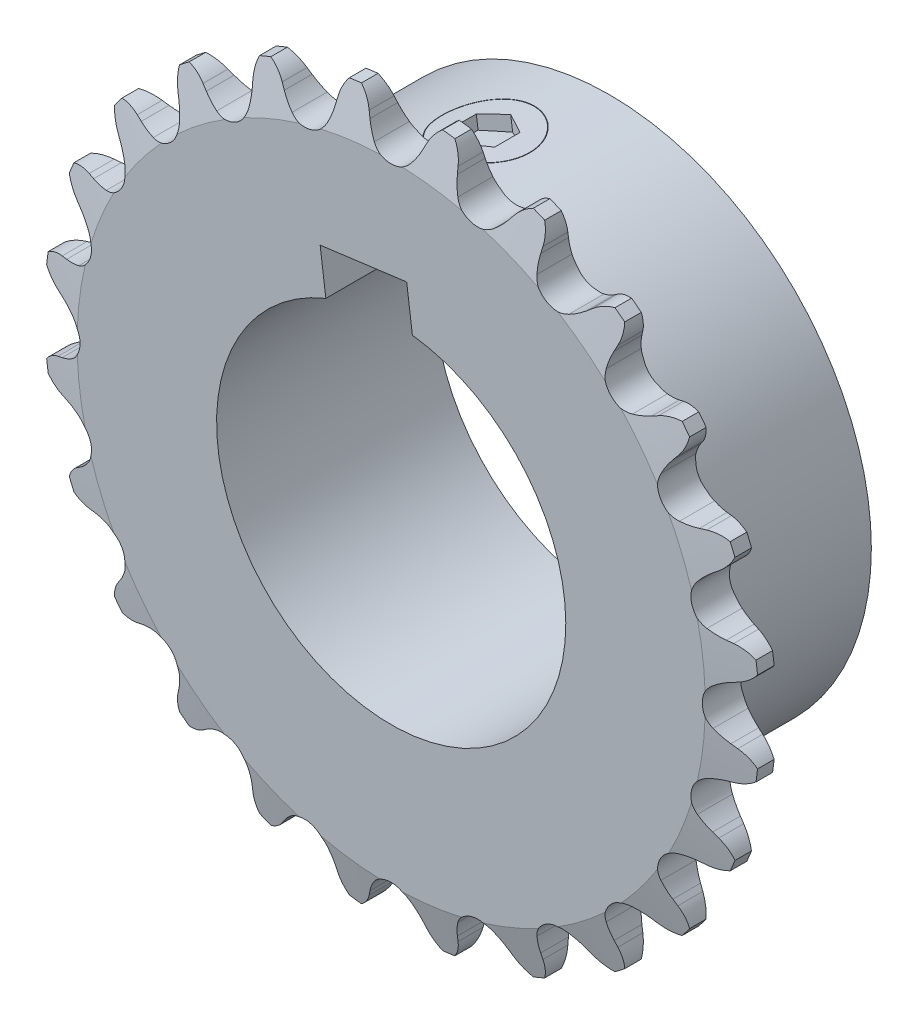
SolidWorks part; units mm, degrees
ref_plane "Front Plane" through (0, 0, 0) normal (0, 0, 1) x (1, 0, 0)
ref_plane "Top Plane" through (0, 0, 0) normal (0, 1, 0) x (1, 0, 0)
ref_plane "Right Plane" through (0, 0, 0) normal (1, 0, 0) x (0, 0, -1)
ref_axis "Axis1" through (0, 0, -88.99) along (0, 0, 1)
sketch "Sprocket-BaseSketch" plane through (0, 0, 0) normal (1, 0, 0) x (0, 0, -1)
  line L0 (1.397, 0) -> (1.397, 22.8465)
  line L1 (1.397, 22.8465) -> (0.6032, 26.0215)
  line L2 (0.6032, 26.0215) -> (-0.6032, 26.0215)
  line L3 (-0.6032, 26.0215) -> (-1.397, 22.8465)
  line L4 (-1.397, 22.8465) -> (-1.397, 0)
  line L5 (-1.397, 0) -> (1.397, 0)
  line L6 (5.588, 0) -> (-1.7463, 0) construction
  dimension "Hub Surface" = 1.397
  dimension "RightSide (1)" = 0.7938
  dimension "RightSide (2)" = 3.175
  dimension "OD" = 26.0215
  dimension "LeftSide (1)" = 0.7938
  dimension "LeftSide (2)" = 3.175
  dimension "Tooth Width" = 2.794
revolve "25 (04C) ANSI (ISO) Chain Number, 1.915in P.D." add sketch "Sprocket-BaseSketch" angle 360 about L6
sketch "Tooth-Sketch" plane through (0, 0, 0) normal (0, 0, 1) x (1, 0, 0)
  line L0 (0, 0) -> (0, 32.4328) construction
  line L1 (1.932, 24.319) -> (2.0923, 24.7192)
  line L2 (-1.932, 24.319) -> (-2.0923, 24.7192)
  line L3 (0, 24.3246) -> (6.2957, 23.4958) construction
  line L4 (0, 24.3246) -> (-6.2957, 23.4958) construction
  arc A0 (-1.3466, 23.2913) -> (1.3466, 23.2913) centre (0, 24.3246) ccw
  arc A1 (1.3466, 23.2913) -> (1.932, 24.319) centre (-2.0957, 25.9327) ccw
  arc A2 (-1.3466, 23.2913) -> (-1.932, 24.319) centre (2.0957, 25.9327) cw
  arc A3 (2.0923, 24.7192) -> (4.5833, 26.4046) centre (4.5833, 23.7212) cw
  arc A4 (-2.0923, 24.7192) -> (-4.5833, 26.4046) centre (-4.5833, 23.7212) ccw
  arc A5 (4.5833, 26.4046) -> (-4.5833, 26.4046) centre (0, 0) ccw
extrude "Tooth-Cut, Number of teeth: 24" cut sketch "Tooth-Sketch" against normal through all and the other way through all
pattern_circular "Tooth Pattern, 24 / 24" count 24 every 15 about axis through (0, 0, -88.99) along (0, 0, 1) of "Tooth-Cut, Number of teeth: 24"
sketch "Sketch3" plane through (0, 0, 0) normal (1, 0, 0) x (0, 0, -1)
  line L0 (-13.081, 0) -> (13.081, 0) construction
  line L1 (1.397, 0) -> (1.397, 19.05)
  line L2 (1.397, 19.05) -> (14.478, 19.05)
  line L3 (14.478, 19.05) -> (14.478, 0)
  line L4 (14.478, 0) -> (1.397, 0)
  dimension "Hub Mounting" = 1.397
  dimension "Hub OD" = 19.05
  dimension "Hub Width" = 13.081
revolve "Hub-Revolve1" add sketch "Sketch3" angle 360 about L0
sketch "Sketch4" plane through (0, 0, -14.478) normal (0, 0, -1) x (-1, 0, 0)
  circle A0 centre (0, 0) radius 12.7
  dimension "Bore Diameter " = 25.4
extrude "Cut-Extrude1" cut sketch "Sketch4" against normal through all
sketch "Sketch5" plane through (0, 0, 0) normal (1, 0, 0) x (0, 0, -1)
  line L0 (14.478, 0) -> (-1.397, 0) construction
  line L1 (14.478, -19.05) -> (14.478, 19.05) construction
  line L2 (-1.397, 0.8085) -> (-1.397, -0.8085) construction
ref_plane "Plane1" through (0, 0, 0) normal (-0.1305, 0.9914, 0) x (-0.9914, -0.1305, 0)
sketch "Sketch6" plane through (0, 0, -14.478) normal (0, 0, -1) x (-1, 0, 0)
  line L0 (-1.5428, 12.6059) -> (-1.1284, 15.7538)
  line L1 (-1.1284, 15.7538) -> (5.1673, 14.9249)
  line L2 (5.1673, 14.9249) -> (4.7529, 11.7771)
  line L3 (4.7529, 11.7771) -> (-1.5428, 12.6059)
  line L4 (8.6566, -1.1397) -> (-8.6566, 1.1397) construction
  circle A0 centre (0, 0) radius 12.7 construction
  dimension "Keyway Wd " = 6.35
  dimension "Keyway Dp " = 3.175
extrude "Cut-Extrude2" cut sketch "Sketch6" against normal through all
sketch "Sketch7" plane through (-2.0195, 15.3394, 0) normal (0.1305, -0.9914, 0) x (0.9914, 0.1305, 0)
  line L0 (0, -14.478) -> (0, -1.397) construction
  line L1 (-2.1786, -1.397) -> (2.1786, -1.397) construction
  line L2 (-3.175, 1.397) -> (-3.175, -14.478) construction
  circle A0 centre (0, -7.9375) radius 3.175
extrude "Cut-Extrude3" cut sketch "Sketch7" against normal through all draft 1 draft outward yes
sketch "Sketch8" plane through (-2.0195, 15.3394, 0) normal (0.1305, -0.9914, 0) x (0.9914, 0.1305, 0)
  line L0 (-3.175, -7.9375) -> (-3.2326, -7.9375) construction
  line L1 (-3.175, 1.397) -> (-3.175, -14.478) construction
  line L2 (-3.2038, -7.9375) -> (-3.2038, -14.478) construction
  line L3 (-19.05, -14.478) -> (19.05, -14.478) construction
  circle A0 centre (0, -7.9375) radius 3.2038
  arc A1 (-3.175, -7.9375) -> (3.175, -7.9375) centre (0, -7.9375) ccw construction
  spline S0 degree 3 poles (-2.797, -9.5747) (-2.5581, -9.9284) (-2.4233, -10.0905) (-2.1245, -10.3867) (-1.9584, -10.522) (-1.6051, -10.7557) (-1.419, -10.8541) (-1.0278, -11.0143) (-0.8212, -11.0759) (-0.4063, -11.1563) (-0.1961, -11.176) (0.23, -11.1738) (0.4428, -11.1514) (0.8561, -11.0665) (1.06, -11.0034) (1.4521, -10.8378) (1.6372, -10.737) (1.9863, -10.5004) (2.1516, -10.3629) (2.4479, -10.0625) (2.5804, -9.8991) (2.8137, -9.5454) (2.9136, -9.3558) (3.0726, -8.9655) (3.1331, -8.7629) (3.2143, -8.3428) (3.2337, -8.1321) (3.2315, -7.7099) (3.2094, -7.4959) (3.1244, -7.08) (3.0621, -6.8785) (2.8984, -6.4883) (2.7961, -6.2991) (2.5603, -5.9498) (2.4262, -5.7875) (2.1243, -5.4879) (1.9595, -5.354) (1.6087, -5.1215) (1.4201, -5.0214) (1.0266, -4.8603) (0.8245, -4.8) (0.4097, -4.7192) (0.1948, -4.699) (-0.2287, -4.7012) (-0.4387, -4.7229) (-0.855, -4.8081) (-1.0599, -4.8717) (-1.4484, -5.0355) (-1.6349, -5.1365) (-1.9876, -5.3754) (-2.1495, -5.5102) (-2.4455, -5.8097) (-2.5808, -5.9765) (-2.8136, -6.3294) (-2.9119, -6.5156) (-3.0719, -6.9074) (-3.1334, -7.1139) (-3.2136, -7.5284) (-3.2336, -7.7388) (-3.2316, -8.1658) (-3.2096, -8.3776) (-3.1254, -8.7911) (-3.0625, -8.9956) (-2.8978, -9.3881) (-2.797, -9.5747) (-2.5581, -9.9284) (-2.4233, -10.0905) knots -0.03125 -0.03125 0 0 0.03125 0.03125 0.0625 0.0625 0.09375 0.09375 0.125 0.125 0.15625 0.15625 0.1875 0.1875 0.21875 0.21875 0.25 0.25 0.28125 0.28125 0.3125 0.3125 0.34375 0.34375 0.375 0.375 0.40625 0.40625 0.4375 0.4375 0.46875 0.46875 0.5 0.5 0.53125 0.53125 0.5625 0.5625 0.59375 0.59375 0.625 0.625 0.65625 0.65625 0.6875 0.6875 0.71875 0.71875 0.75 0.75 0.78125 0.78125 0.8125 0.8125 0.84375 0.84375 0.875 0.875 0.90625 0.90625 0.9375 0.9375 0.96875 0.96875 1 1 1.03125 1.03125 1.0625 only from (-2.6775, -9.7515) to (-2.6775, -9.7515) construction
extrude "Extrude1" add sketch "Sketch8" against normal up to surface (3.3069 mm away) up to face at (-0.2607, 19.0482, -5.5916)
sketch "Sketch9" plane through (-2.0195, 15.3394, 0) normal (0.1305, -0.9914, 0) x (0.9914, 0.1305, 0)
  line L0 (0, -7.9375) -> (3.2038, -7.9375) construction
  line L1 (1.6019, -7.9375) -> (1.6019, -10.7121) construction
  line L3 (0, -9.7872) -> (1.6019, -8.8624)
  line L4 (1.6019, -8.8624) -> (1.6019, -7.0126)
  line L5 (1.6019, -7.0126) -> (0, -6.0878)
  line L6 (0, -6.0878) -> (-1.6019, -7.0126)
  line L7 (-1.6019, -7.0126) -> (-1.6019, -8.8624)
  line L8 (-1.6019, -8.8624) -> (0, -9.7872)
  circle A0 centre (0, -7.9375) radius 3.2038 construction
  circle A1 centre (0, -7.9375) radius 1.6019 construction
extrude "Cut-Extrude4" cut sketch "Sketch9" against normal through all from offset 2.54 offset against normal yes
sketch "Sketch10" plane through (0, 0, -14.478) normal (0, 0, -1) x (-1, 0, 0)
  line L0 (-25.7989, 3.3965) -> (25.7989, -3.3965)
  line L1 (-6.2957, -23.4958) -> (0, -24.3246)
  line L2 (8.6566, -1.1397) -> (-8.6566, 1.1397) construction
  line L3 (-26.0277, 1.6589) -> (25.5701, -5.1341)
  line L4 (-6.0669, -21.7582) -> (0.2288, -22.587)
  circle A0 centre (0, 0) radius 26.0215
  circle A1 centre (0, 0) radius 12.7
  arc A2 (-1.5428, 12.6059) -> (4.7529, 11.7771) centre (0, 0) ccw construction
  arc A3 (20.9127, 15.4848) -> (20.3698, 16.1923) centre (0, 0) ccw construction
  dimension "D1" = 1.7526
  dimension "D2" = 1.7526
equation "\"D1@Sketch10\" = \"D2@Sketch10\""
